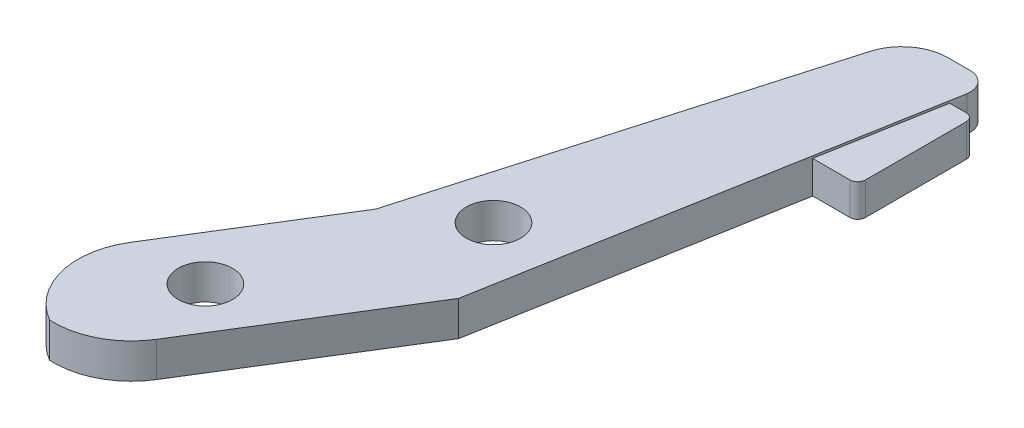
SolidWorks part; units mm, degrees
ref_plane "Front Plane" through (0, 0, 0) normal (0, 0, 1) x (1, 0, 0)
ref_plane "Top Plane" through (0, 0, 0) normal (0, 1, 0) x (1, 0, 0)
ref_plane "Right Plane" through (0, 0, 0) normal (1, 0, 0) x (0, 0, -1)
sketch "Sketch1" plane through (0, 0, 0) normal (0, 1, 0) x (1, 0, 0)
  line L0 (0, 0) -> (9.4812, 15.3005)
  line L1 (9.4812, 15.3005) -> (17.2343, 42.2057)
  line L6 (17.1409, 12.992) -> (7.6597, -2.3085)
  line L7 (7.6597, -2.3085) -> (0, 0)
  line L9 (17.1409, 12.992) -> (22.3475, 42.2057)
  line L10 (22.3475, 42.2057) -> (17.2343, 42.2057)
  point P2 (22.929, 42.4883)
  point P6 (17.1409, 42.2057)
  dimension "D1" = 8
  dimension "D2" = 18
  dimension "D3" = 18
  dimension "D4" = 28
extrude "Boss-Extrude1" add sketch "Sketch1" along normal blind 2.25
fillet "Fillet1" radius 5 2 edges at (7.6597, 1.125, 2.3085) (0, 1.125, 0)
sketch "Sketch2" plane through (0, 2.25, 0) normal (0, 1, 0) x (1, 0, 0)
  line L0 (17.1409, 12.992) -> (22.3475, 42.2057) construction
  line L1 (9.6801, 0.952) -> (17.1409, 12.992) construction
  circle A0 centre (8.1672, 5.6299) radius 1.75
  circle A1 centre (14.0315, 18.3425) radius 1.75
  dimension "D1" = 3.5
  dimension "D2" = 3.5
  dimension "D3" = 14
  dimension "D4" = 4
  dimension "D5" = 3.75
extrude "Cut-Extrude1" cut sketch "Sketch2" against normal through all
ref_plane "Plane1" through (23.5, 0, 0) normal (1, 0, 0) x (0, 0, -1)
sketch "Sketch4" plane through (23.5, -1.4847, -8.2019) normal (1, 0, 0) x (0, 0, -1)
  line L1 (31.6585, 3.5919) -> (24.1585, 3.5919)
  line L2 (31.6585, 3.5919) -> (31.6585, 1.4919)
  line L3 (31.6585, 1.4919) -> (24.1585, 1.4919)
  line L4 (24.1585, 3.5919) -> (24.1585, 1.4919)
  dimension "D1" = 2.1
  dimension "D2" = 7.5
extrude "Boss-Extrude2" add sketch "Sketch4" against normal up to surface (1.5705 mm away) up to face at (19.7442, 1.125, -27.5989)
extrude "Boss-Extrude3" add sketch "Sketch4<2>" against normal up to surface (1.5705 mm away) up to face at (21.2611, 1.0572, -36.1104)
sketch "Sketch4<2>" plane through (23.5, -1.4847, -8.2019) normal (1, 0, 0) x (0, 0, -1) same geometry as "Sketch4"
fillet "Fillet2" radius 3 1 edges at (17.2343, 1.125, -42.2057)
fillet "Fillet3" radius 1.2 1 edges at (22.3475, 1.125, -42.2057)
fillet "Fillet4" radius 0.5 2 edges at (23.5, 1.0572, -32.3604) (23.5, 1.0572, -39.8604)
